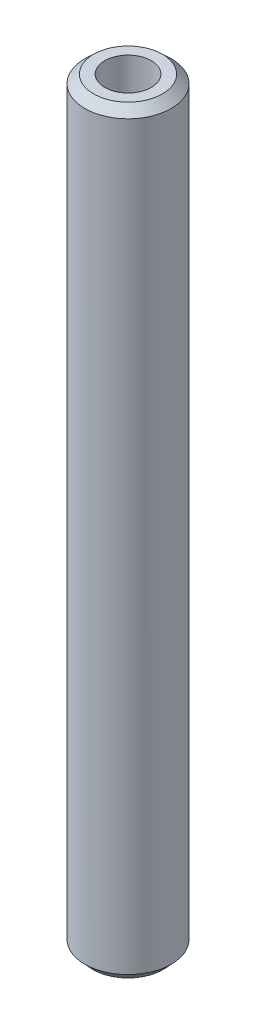
SolidWorks part; units mm, degrees
ref_plane "Front Plane" through (0, 0, 0) normal (0, 0, 1) x (1, 0, 0)
ref_plane "Top Plane" through (0, 0, 0) normal (0, 1, 0) x (1, 0, 0)
ref_plane "Right Plane" through (0, 0, 0) normal (1, 0, 0) x (0, 0, -1)
sketch "Sketch1" plane through (0, 0, 0) normal (0, 1, 0) x (1, 0, 0)
  circle A0 centre (0, 0) radius 20
  dimension "SHAFT_OD" = 40
extrude "Boss-Extrude1" add sketch "Sketch1" along normal blind 351.1469
sketch "Sketch2" plane through (0, 0, 0) normal (0, 1, 0) x (1, 0, 0)
  circle A0 centre (0, 0) radius 10.7671
  dimension "BORE_D" = 21.5342
extrude "Cut-Extrude1" cut sketch "Sketch2" along normal through all
chamfer "Chamfer1" distance 3.8209 angle 46.792 2 edges at (0, 351.1469, 20) (0, 0, 20) first distance on face at (0, 351.1469, 20) first distance on face at (0, 0, 10.7671)
